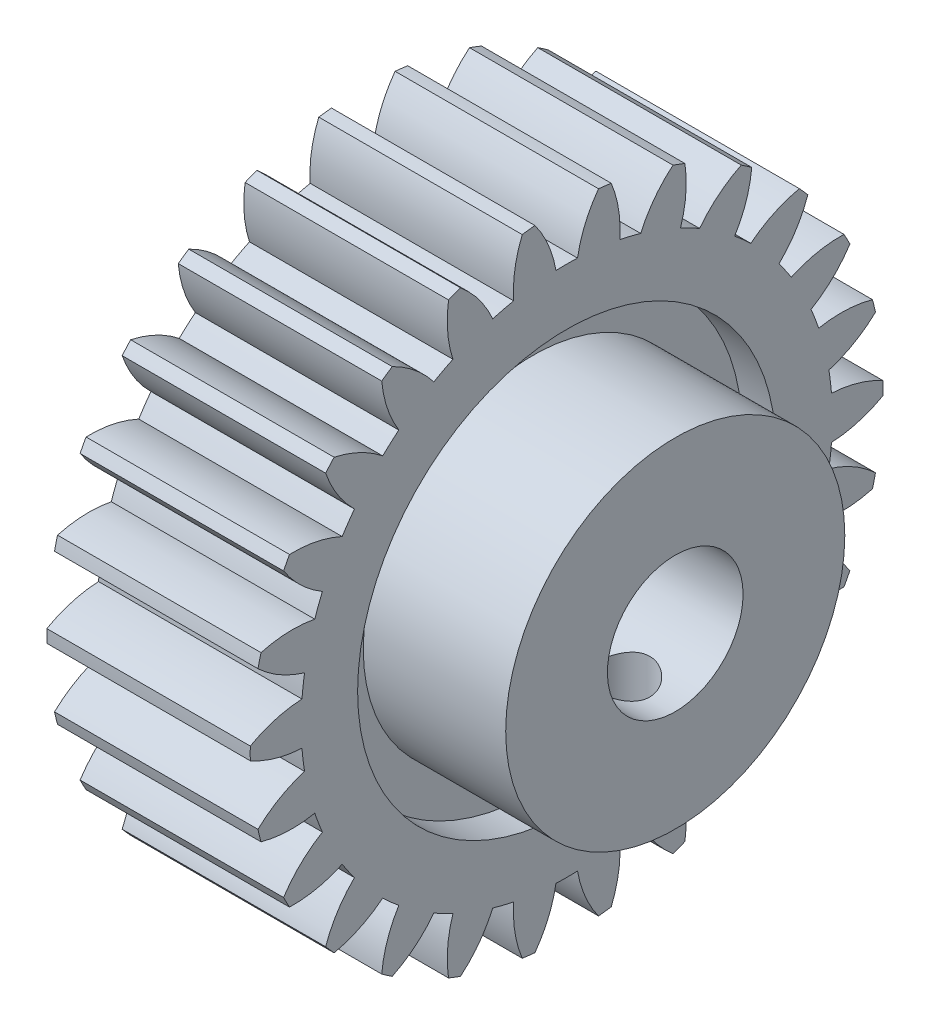
SolidWorks part; units mm, degrees
ref_plane "Plane1" through (0, 0, 0) normal (0, 0, 1) x (1, 0, 0)
ref_plane "Plane2" through (0, 0, 0) normal (0, 1, 0) x (1, 0, 0)
ref_plane "Plane3" through (0, 0, 0) normal (1, 0, 0) x (0, 0, -1)
other "Configuration Table"
sketch "HoldingSke" plane through (0, 0, 0) normal (0, 1, 0) x (1, 0, 0)
  line L0 (0, 0) -> (0.8988, -0.4384)
  line L1 (-15, 0) -> (100, 0) construction
  line L2 (0, 0) -> (-2.1039, 2.3779)
  line L3 (0, 0) -> (-11.863, 4.5341)
  line L4 (0, 0) -> (7.762, 3.7858)
  line L5 (0, 0) -> (-16.8652, -6.2902)
  line L6 (0, 0) -> (-7.4607, -5.0337)
  line L7 (-2.1039, 2.3779) -> (1.7706, 19.956)
  line L8 (-76.2, 54.61) -> (-75.2, 54.61)
  line L9 (-71.009, 38.7566) -> (-53.1078, 45.2721)
  line L10 (-76.2, 71.12) -> (104.1128, 71.12)
  line L11 (0, 0) -> (-9, 0)
  line L12 (-76.2, 101.6) -> (-76.162, 101.6)
  line L13 (24.9733, 27.94) -> (52.9518, 28.4284)
  line L14 (24.9733, 27.94) -> (24.9743, 27.94)
  line L15 (24.9733, 27.94) -> (100.4006, 29.5858)
  line L16 (-63.627, -1) -> (-12.827, -1)
  circle A0 centre (0, 0) radius 3
  circle A1 centre (0, 0) radius 7.5
  circle A2 centre (0, 0) radius 7.5
  circle A3 centre (0, 0) radius 3
  dimension "Num_teeth" = 26
  dimension "Pitch_radius" = 180.3128
  dimension "Width" = 9
  dimension "Thickness" = 9
sketch "BasProSke" plane through (0, 0, 0) normal (0, 1, 0) x (1, 0, 0)
  line L0 (-10, 0) -> (60, 0) construction
  line L1 (0, 0) -> (0, 14)
  line L2 (0, 0) -> (9, 0)
  line L3 (9, 0) -> (9, 14)
  line L4 (9, 14) -> (0, 14)
  dimension "Thickness" = 9
  dimension "Diameter" = 28
revolve "Base-Revolve" add sketch "BasProSke" angle 360 about L0
sketch "TooCutSke" plane through (0, 0, 0) normal (1, 0, 0) x (0, 0, -1)
  line L1 (0, 0) -> (0, 107) construction
  line L2 (0, 0) -> (-0.8514, 12.9721) construction
  line L3 (0, 0) -> (-3.1292, 25.771) construction
  line L4 (-0.8514, 12.9721) -> (-1.5646, 12.8855) construction
  arc A0 (0.477, 11.7393) -> (-0.477, 11.7393) centre (0, 0) ccw
  arc A1 (1.4241, 13.9529) -> (-1.4241, 13.9529) centre (0, 0) ccw
  circle A2 centre (0, 0) radius 13 construction
  circle A3 centre (0, 0) radius 12.216 construction
  arc A4 (-0.477, 11.7393) -> (-1.4241, 13.9529) centre (-5.6014, 10.8561) ccw
  arc A5 (1.4241, 13.9529) -> (0.477, 11.7393) centre (5.6014, 10.8561) ccw
extrude "ToothCut" cut sketch "TooCutSke" along normal through all
fillet "Breaks" [suppressed] radius 0.02 tangent propagation no
fillet "RootFillets" [suppressed] radius 0.251
pattern_circular "TeethCuts" count 26 every 13.846 about axis through (-10, 0, 0) along (1, 0, 0) of "ToothCut", "RootFillets", "Breaks"
sketch "HubNeaOneSke" plane through (0, 0, 0) normal (-1, 0, 0) x (0, 0, 1)
  circle A0 centre (0, 0) radius 7.5
  dimension "Diameter" = 15
extrude "HubNearOne" add sketch "HubNeaOneSke" along normal blind 9.0001
sketch "HubNeaBotSke" plane through (0, 0, 0) normal (-1, 0, 0) x (0, 0, 1)
  circle A0 centre (0, 0) radius 7.5
  dimension "Diameter" = 15
extrude "HubNearBoth" [suppressed] add sketch "HubNeaBotSke" along normal blind 4.5
ref_plane "FarPln" through (9, 0, 0) normal (1, 0, 0) x (0, 0, -1)
sketch "HubFarSke" plane through (9, 0, 0) normal (1, 0, 0) x (0, 0, -1)
  circle A0 centre (0, 0) radius 7.5
  dimension "Diameter" = 15
extrude "HubFar" [suppressed] add sketch "HubFarSke" along normal blind 4.5
sketch "BorSke" plane through (0, 0, 0) normal (1, 0, 0) x (0, 0, -1)
  circle A0 centre (0, 0) radius 3
  dimension "Diameter" = 6
extrude "Bore" cut sketch "BorSke" along normal mid plane 36.0001
sketch "KeySke" plane through (0, 0, 0) normal (1, 0, 0) x (0, 0, -1)
  line L0 (-1, 0) -> (-1, 4)
  line L1 (-1, 4) -> (1, 4)
  line L2 (1, 4) -> (1, 0)
  line L3 (0, 0) -> (0, 34) construction
  line L4 (-1, 0) -> (1, 0)
  dimension "Width" = 2
extrude "Keyway" [suppressed] cut sketch "KeySke" along normal mid plane 36.0001
pattern_circular "Keyway2" [suppressed] count 2 every 90 about axis through (-10, 0, 0) along (1, 0, 0) reverse direction yes
sketch "Sketch1" plane through (0, 0, 0) normal (0, 0, 1) x (1, 0, 0)
  line L1 (-9.0001, 7.5) -> (-2.7, 7.5)
  line L2 (-9.0001, 7.5) -> (-9.0001, -7.5238)
  line L3 (-9.0001, -7.5238) -> (-2.7, -7.5238)
  line L4 (-2.7, 7.5) -> (-2.7, -7.5238)
  line L5 (0, 7.5) -> (0, -7.5) construction
  dimension "D1" = 2.7
extrude "Cut-Extrude1" cut sketch "Sketch1" against normal through all both and the other way through all
sketch "Sketch2" plane through (9, 0, 0) normal (1, 0, 0) x (0, 0, -1)
  circle A0 centre (0, 0) radius 9.25
  circle A1 centre (0, 0) radius 7.5 construction
  circle A2 centre (0, 0) radius 7.5
  dimension "D1" = 18.5
extrude "Cut-Extrude2" cut sketch "Sketch2" against normal blind 1.5
extrude "Cut-Extrude3" cut sketch "Sketch2<2>" along normal blind 1.5 from surface starting at face at (0, 0, -7.5)
sketch "Sketch2<2>" plane through (9, 0, 0) normal (1, 0, 0) x (0, 0, -1) same geometry as "Sketch2"
sketch "Sketch3" plane through (9, 0, 0) normal (1, 0, 0) x (0, 0, -1)
  circle A1 centre (0, 0) radius 7.5
  circle A2 centre (0, 0) radius 7.5
  circle M2 centre (0, 0) radius 3
  circle M3 centre (0, 0) radius 7.5
  dimension "D1" = 0
extrude "Boss-Extrude1" add sketch "Sketch3" along normal blind 4.8 contours M3 M2 region at (9, 0, 7.2879)
sketch "Sketch5" plane through (0, 0, 0) normal (0, 1, 0) x (1, 0, 0)
  line L0 (9, -0.477) -> (9, 0.477) construction
  circle A0 centre (11.4, 0) radius 1.275
  dimension "D1" = 2.55
  dimension "D2" = 2.4
extrude "Cut-Extrude4" cut sketch "Sketch5" against normal up to next
equation "' \"Module@HoldingSke\" = 6.35"
equation "' \"Num_teeth@HoldingSke\" = 12"
equation "' \"Ap@HoldingSke\" =  20"
equation "' \"Ap@HoldingSke\" = 20"
equation "' \"Width@HoldingSke\" = 0.5 * 25.4"
equation "' \"Hub_dia@HoldingSke\"= 1 * 25.4"
equation "' \"Hub_dia@HoldingSke\" = 1 * 25.4"
equation "' \"Overall_len@HoldingSke\" = 1.0 * 25.4"
equation "' \"Bore@HoldingSke\" = 0.75 * 25.4"
equation "' \"T_dim@HoldingSke\" = 0.1 * 25.4"
equation "' \"Width@KeySke\" = 0.25 * 25.4"
equation "' \"Show_teeth@HoldingSke\" = 13"
equation "' \"Backlash@HoldingSke\" = 0.009 * 25.4"
equation "' \"Addendum_fac@HoldingSke\" = 1.0"
equation "' \"Dedendum_fac@HoldingSke\" = 1.25"
equation "' \"Dedendum_add@HoldingSke\" = 0.00005 * 25.4"
equation "' \"Clearance_fac@HoldingSke\" = 0.25"
equation "\"Pitch@HoldingSke\" = 1 / \"Module@HoldingSke\""
equation "\"Overcut_dia@TooCutSke\" = (\"Num_teeth@HoldingSke\" + 2 * \"Addendum_fac@HoldingSke\") / \"Pitch@HoldingSke\" + 0.002 * 25.4"
equation "\"Pitch_dia@TooCutSke\" = \"Num_teeth@HoldingSke\" / \"Pitch@HoldingSke\""
equation "\"Base_dia@TooCutSke\" = \"Num_teeth@HoldingSke\" / \"Pitch@HoldingSke\" * cos((\"Ap@HoldingSke\"  * 3.14159265 / 180))"
equation "\"Root_dia@TooCutSke\" = (\"Num_teeth@HoldingSke\" + 2) / \"Pitch@HoldingSke\" - 2 * (\"Addendum_fac@HoldingSke\" + \"Dedendum_fac@HoldingSke\") / \"Pitch@HoldingSke\" - \"Dedendum_add@HoldingSke\" * 2"
equation "\"Half_ang@TooCutSke\" = 180 / \"Num_teeth@HoldingSke\""
equation "\"Half_CT@TooCutSke\" = \"Num_teeth@HoldingSke\" / \"Pitch@HoldingSke\" * sin((3.14159265 / 2 / \"Num_teeth@HoldingSke\")) / 2 - 7 * \"Backlash@HoldingSke\" / 4"
equation "\"Flank_rad@TooCutSke\" = \"Num_teeth@HoldingSke\" / \"Pitch@HoldingSke\" / 5"
equation "\"Radius@RootFillets\" = \"Clearance_fac@HoldingSke\" / \"Pitch@HoldingSke\" + \"Dedendum_add@HoldingSke\""
equation "\"Break_rad@Breaks\" = 0.02 / \"Pitch@HoldingSke\""
equation "\"Thickness@HoldingSke\" = \"Width@HoldingSke\""
equation "\"OAL@HoldingSke\" = \"Thickness@HoldingSke\""
equation "\"MHD@HoldingSke\" = (\"Num_teeth@HoldingSke\" + 2) / \"Pitch@HoldingSke\" - 2 * (\"Addendum_fac@HoldingSke\" + \"Dedendum_fac@HoldingSke\")  / \"Pitch@HoldingSke\" - \"Dedendum_add@HoldingSke\" * 2"
equation "\"MBD@HoldingSke\" = (\"Num_teeth@HoldingSke\" + 2) / \"Pitch@HoldingSke\" - 2 * (\"Addendum_fac@HoldingSke\" + \"Dedendum_fac@HoldingSke\")  / \"Pitch@HoldingSke\" - \"Dedendum_add@HoldingSke\" * 2 - 0.002 * 25.4"
equation "\"MHD@HoldingSke\" = ((sgn( \"MHD@HoldingSke\" - \"Hub_dia@HoldingSke\" )-1)*( \"MHD@HoldingSke\" - \"Hub_dia@HoldingSke\" ))/-2+ \"Hub_dia@HoldingSke\""
equation "\"MBD@HoldingSke\" = ((sgn( \"MBD@HoldingSke\" - \"Bore@HoldingSke\" )-1)*( \"MBD@HoldingSke\" - \"Bore@HoldingSke\" ))/-2+ \"Bore@HoldingSke\""
equation "\"OAL@HoldingSke\" = ((sgn( \"OAL@HoldingSke\" - \"Overall_len@HoldingSke\" )+1)*( \"OAL@HoldingSke\" - \"Overall_len@HoldingSke\" ))/2 + \"Overall_len@HoldingSke\" + 0.000002 * 25.4"
equation "\"Num_teeth@TeethCuts\" = int( \"Show_teeth@HoldingSke\" ) + 1"
equation "\"Num_teeth@TeethCuts\" = ((sgn( \"Num_teeth@TeethCuts\" - \"Num_teeth@HoldingSke\" )-1)*( \"Num_teeth@TeethCuts\" - \"Num_teeth@HoldingSke\" ))/-2+ \"Num_teeth@HoldingSke\""
equation "\"Num_teeth@TeethCuts\" = ((sgn( \"Num_teeth@TeethCuts\" - 2.0)+1)*( \"Num_teeth@TeethCuts\" - 2.0))/2 +2.0"
equation "\"Angle@TeethCuts\" = 360.0 / \"Num_teeth@HoldingSke\""
equation "\"Diameter@BasProSke\" = (\"Num_teeth@HoldingSke\" + 2 * \"Addendum_fac@HoldingSke\") / \"Pitch@HoldingSke\""
equation "\"Thickness@BasProSke\"  = \"Thickness@HoldingSke\""
equation "' \"Fillet_rad@BasProSke\" =  \"Thickness@HoldingSke\" * 0.05"
equation "' \"Fillet_rad@BasProSke\" = \"Thickness@HoldingSke\" * 0.05"
equation "\"MHD@HoldingSke\" = ((sgn( \"MHD@HoldingSke\" - \"Root_dia@TooCutSke\" )-1)*( \"MHD@HoldingSke\" - \"Root_dia@TooCutSke\" ))/-2+ \"Root_dia@TooCutSke\""
equation "\"Diameter@HubNeaOneSke\" = \"MHD@HoldingSke\""
equation "\"Length@HubNearOne\" = \"OAL@HoldingSke\" - \"Thickness@BasProSke\""
equation "\"Diameter@HubNeaBotSke\" = \"MHD@HoldingSke\""
equation "\"Length@HubNearBoth\" = ( \"OAL@HoldingSke\" - \"Thickness@BasProSke\" ) / 2.0"
equation "\"Thickness@FarPln\" = \"Thickness@BasProSke\""
equation "\"Diameter@HubFarSke\" = \"MHD@HoldingSke\""
equation "\"Length@HubFar\" = ( \"OAL@HoldingSke\" - \"Thickness@BasProSke\" ) / 2.0"
equation "\"Diameter@BorSke\" = \"MBD@HoldingSke\""
equation "\"D1@Bore\" = \"OAL@HoldingSke\" * 2.0"
equation "\"D1@Keyway\" = \"OAL@HoldingSke\" * 2.0"
equation "\"Offset@KeySke\" = \"T_dim@HoldingSke\" + \"MBD@HoldingSke\" / 2.0"
equation "\"D1@Sketch4\"= 2mm"
